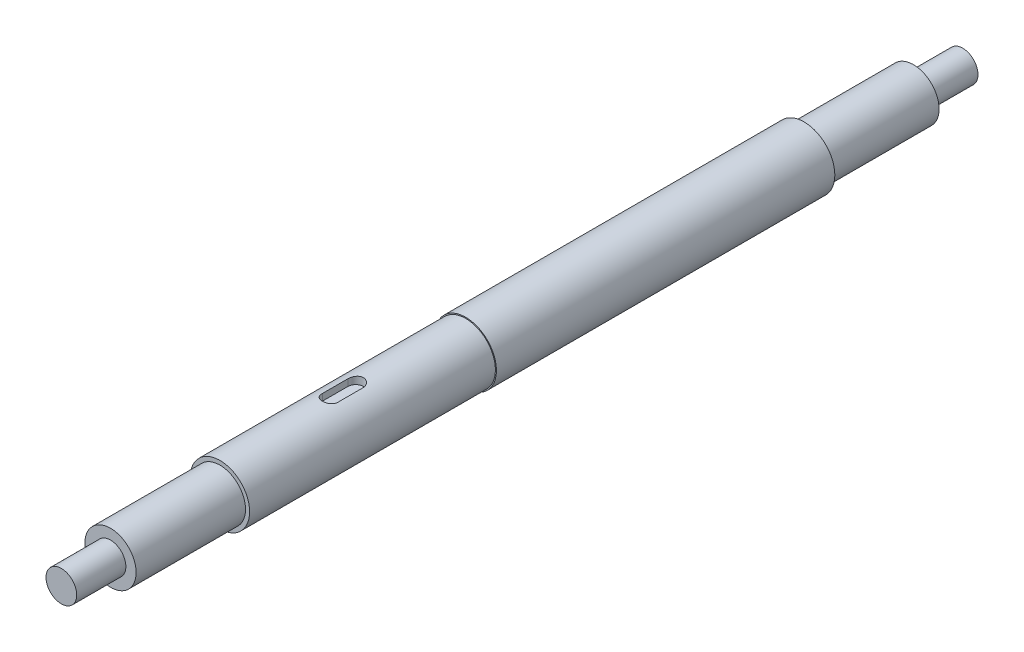
SolidWorks part; units mm, degrees
material "Alloy Steel"
ref_plane "Front Plane" through (0, 0, 0) normal (0, 0, 1) x (1, 0, 0)
ref_plane "Top Plane" through (0, 0, 0) normal (0, 1, 0) x (1, 0, 0)
ref_plane "Right Plane" through (0, 0, 0) normal (1, 0, 0) x (0, 0, -1)
sketch "Sketch1" plane through (0, 0, 0) normal (0, 0, 1) x (1, 0, 0)
  circle A0 centre (0, 0) radius 9.525
  dimension "D1" = 19.05
extrude "Boss-Extrude1" add sketch "Sketch1" along normal mid plane 279.4
ref_plane "Plane1" through (0, 0, 90.551) normal (0, 0, 1) x (1, 0, 0)
sketch "Sketch3" plane through (0, 0, 90.551) normal (0, 0, 1) x (1, 0, 0)
  circle A0 centre (0, 0) radius 7.9375
  circle A1 centre (0, 0) radius 9.525
  circle A2 centre (0, 0) radius 9.525
  dimension "D2" = 15.875
  dimension "D1" = 0
extrude "Cut-Extrude1" cut sketch "Sketch3" along normal up to next
mirror "Mirror1" about plane through (0, 0, 0) normal (0, 0, 1) of "Cut-Extrude1"
ref_plane "Plane2" through (0, 0, 124.46) normal (0, 0, 1) x (1, 0, 0)
sketch "Sketch4" plane through (0, 0, 124.46) normal (0, 0, 1) x (1, 0, 0)
  circle A0 centre (0, 0) radius 4.7625
  circle A1 centre (0, 0) radius 7.9375
  circle A2 centre (0, 0) radius 7.9375
  dimension "D2" = 9.525
  dimension "D1" = 0
extrude "Cut-Extrude2" cut sketch "Sketch4" along normal up to next
mirror "Mirror2" about plane through (0, 0, 0) normal (0, 0, 1) of "Cut-Extrude2"
sketch "Sketch5" plane through (0, 0, 90.551) normal (0, 0, 1) x (1, 0, 0)
  circle A0 centre (0, 0) radius 9.525 construction
  circle A1 centre (0, 0) radius 9.525
  circle A2 centre (0, 0) radius 9.2075
  dimension "D1" = 18.415
extrude "Cut-Extrude3" cut sketch "Sketch5" against normal blind 76.2
ref_plane "Plane3" through (0, 9.2075, 0) normal (0, 1, 0) x (1, 0, 0)
sketch "Sketch6" plane through (0, 9.2075, 0) normal (0, 1, 0) x (1, 0, 0)
  line L0 (-9.525, -14.351) -> (9.525, -14.351) construction
  line L1 (-9.2075, -90.551) -> (9.2075, -90.551) construction
  line L2 (-9.525, -14.351) -> (9.525, -14.351)
  line L3 (-9.2075, -90.551) -> (9.2075, -90.551)
  line L4 (0, -90.551) -> (0, -14.351) construction
  line L5 (-9.2075, -52.451) -> (9.2075, -52.451) construction
  line L6 (-9.2075, -14.351) -> (-9.2075, -90.551) construction
  line L7 (9.2075, -90.551) -> (9.2075, -14.351) construction
  line L8 (0, -56.4198) -> (0, -48.4822) construction
  line L9 (-2.3813, -56.4198) -> (-2.3813, -48.4822)
  line L10 (2.3812, -56.4198) -> (2.3812, -48.4822)
  line L11 (0, -46.101) -> (-5.2744, -46.101) construction
  line L12 (0, -58.801) -> (-5.6689, -58.801) construction
  arc A0 (-2.3813, -56.4198) -> (2.3812, -56.4198) centre (0, -56.4198) ccw
  arc A1 (2.3812, -48.4822) -> (-2.3813, -48.4822) centre (0, -48.4822) ccw
  point P14 (0, -52.451)
  dimension "D1" = 4.7625
  dimension "D2" = 12.7
  dimension "D3" = 38.1
extrude "Cut-Extrude4" cut sketch "Sketch6" against normal blind 2.3812 contours L10 A1 L9 A0 region at (0, 9.2075, 52.451)
